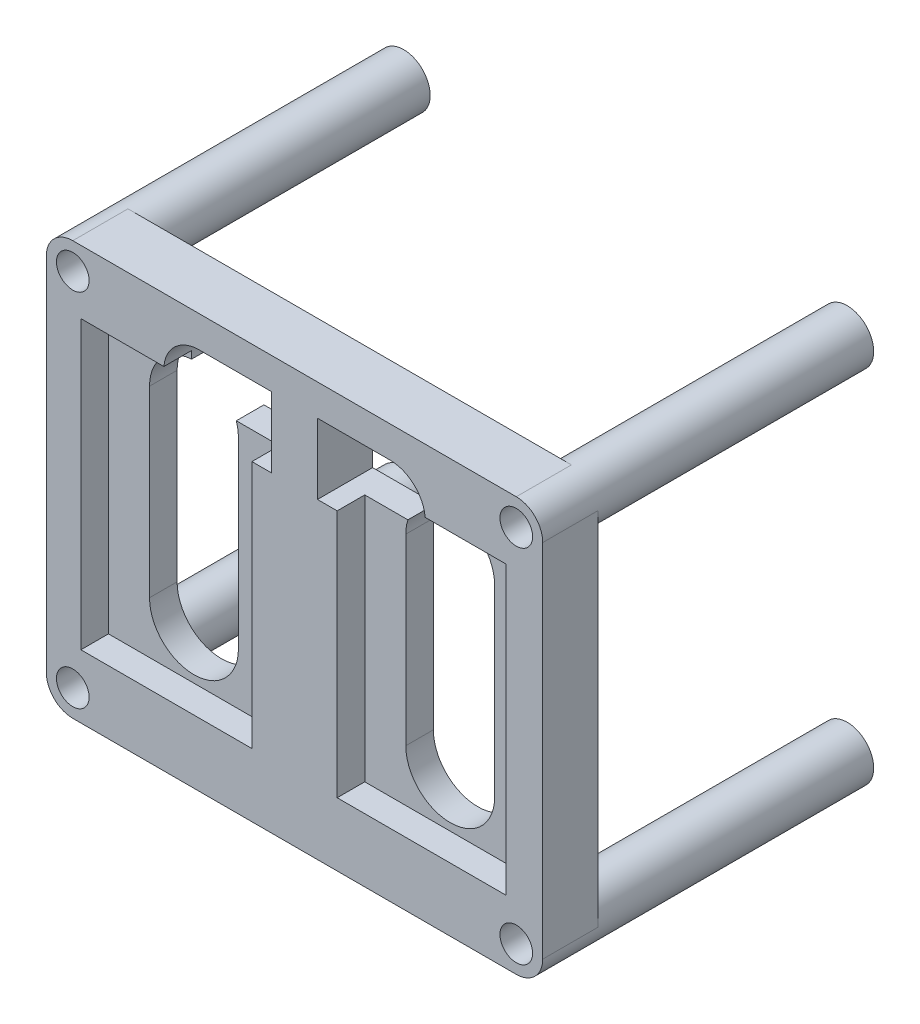
SolidWorks part; units mm, degrees
ref_plane "Front Plane" through (0, 0, 0) normal (0, 0, 1) x (1, 0, 0)
ref_plane "Top Plane" through (0, 0, 0) normal (0, 1, 0) x (1, 0, 0)
ref_plane "Right Plane" through (0, 0, 0) normal (1, 0, 0) x (0, 0, -1)
other "Configuration Table"
sketch "草图1" plane through (0, 0, 0) normal (0, 0, 1) x (1, 0, 0)
  line L0 (0, 0) -> (83.8895, 0) construction
  line L1 (-80.4073, 75) -> (80.4073, 75)
  line L2 (-90, 65.4073) -> (-90, -65.4073)
  line L3 (-80.4073, -75) -> (80.4073, -75)
  line L4 (90, 65.4073) -> (90, -65.4073)
  line L5 (-90, 75) -> (90, -75) construction
  line L6 (-90, -75) -> (90, 75) construction
  line L7 (0, 0) -> (0, -55.7173) construction
  line L8 (-77.464, 52) -> (-15.464, 52)
  line L9 (-77.464, -52) -> (-15.464, -52)
  line L10 (-77.464, 52) -> (-77.464, -52)
  line L11 (76.7565, -52) -> (76.7565, 52)
  line L12 (-15.464, 52) -> (-15.464, -52)
  line L13 (15.464, 52) -> (15.464, -52)
  line L14 (15.464, 52) -> (76.7565, 52)
  line L15 (15.464, -52) -> (76.7565, -52)
  line L16 (-46.464, 52) -> (-46.464, -52) construction
  line L17 (46.1102, -52) -> (46.1102, 52) construction
  line L18 (-46.464, 33.2159) -> (-46.464, -33.2159) construction
  line L19 (-30.3483, 33.2159) -> (-30.3483, -33.2159)
  line L20 (-62.5796, 33.2159) -> (-62.5796, -33.2159)
  line L21 (46.464, 33.2159) -> (46.464, -33.2159) construction
  line L22 (30.3483, 33.2159) -> (30.3483, -33.2159)
  line L23 (62.5796, 33.2159) -> (62.5796, -33.2159)
  line L24 (34.6697, 50.8589) -> (-34.6697, 50.8589) construction
  line L25 (34.6697, 38.0987) -> (-34.6697, 38.0987)
  line L26 (34.6697, 63.6191) -> (-34.6697, 63.6191)
  line L27 (0, 38.0987) -> (0, 63.6191) construction
  line L28 (-8.3233, 38.0987) -> (-8.3233, 63.6191)
  line L29 (8.3233, 38.0987) -> (8.3233, 63.6191)
  arc A1 (-80.4073, 75) -> (-90, 65.4073) centre (-80.4073, 65.4073) ccw
  arc A2 (80.4073, 75) -> (90, 65.4073) centre (80.4073, 65.4073) cw
  arc A3 (-80.4073, -75) -> (-90, -65.4073) centre (-80.4073, -65.4073) cw
  arc A4 (80.4073, -75) -> (90, -65.4073) centre (80.4073, -65.4073) ccw
  arc A5 (-30.3483, 33.2159) -> (-62.5796, 33.2159) centre (-46.464, 33.2159) ccw
  arc A6 (-62.5796, -33.2159) -> (-30.3483, -33.2159) centre (-46.464, -33.2159) ccw
  arc A7 (30.3483, 33.2159) -> (62.5796, 33.2159) centre (46.464, 33.2159) cw
  arc A8 (62.5796, -33.2159) -> (30.3483, -33.2159) centre (46.464, -33.2159) cw
  circle A9 centre (-80.4073, 65.4073) radius 9.5927
  circle A10 centre (80.4073, 65.4073) radius 9.5927
  circle A11 centre (-80.4073, -65.4073) radius 9.5927
  circle A12 centre (80.4073, -65.4073) radius 9.5927
  arc A13 (34.6697, 38.0987) -> (34.6697, 63.6191) centre (34.6697, 50.8589) ccw
  arc A14 (-34.6697, 63.6191) -> (-34.6697, 38.0987) centre (-34.6697, 50.8589) ccw
  arc A15 (-8.3233, 38.0987) -> (8.3233, 38.0987) centre (0, 38.0987) ccw
  arc A16 (8.3233, 63.6191) -> (-8.3233, 63.6191) centre (0, 63.6191) ccw
  circle A17 centre (-80.4073, 65.4073) radius 5.9233
  circle A18 centre (80.4073, 65.4073) radius 5.9233
  circle A19 centre (-80.4073, -65.4073) radius 5.9233
  circle A20 centre (80.4073, -65.4073) radius 5.9233
  point P0 (0, 0)
  point P36 (-46.464, 0)
  point P43 (46.464, 0)
  point P55 (0, 50.8589)
  point P61 (0, 50.8589)
  dimension "D1" = 62
  dimension "D3" = 52
extrude "凸台-拉伸1" add sketch "草图1" along normal blind 20 contours A12 L4 A10 L1 A9 L2 A11 L3 L8 L12 L9 L10 L15 L13 L14 L11 region at (0.5038, -7.9832, 0)
extrude "凸台-拉伸2" add sketch "草图1<3>" along normal blind 10 contours L13 L15 L11 L14 L23 A8 L22 A7 | L12 L8 L10 L9 A6 L20 A5 L19 region at (-62.4214, 50.7892, 0) region at (23.2849, 36.8915, 0)
sketch "草图1<3>" plane through (0, 0, 0) normal (0, 0, 1) x (1, 0, 0) same geometry as "草图1"
extrude "凸台-拉伸3" add sketch "草图1<4>" along normal blind 20 contours L25 A13 A7 | A7 A13 L14 L13 L25 | L14 A13 L26 L29 L25 L13 | L26 A14 L8 L12 L25 L28 | L8 A14 A5 L25 L12 | A5 A14 L25 region at (-23.6937, 55.1681, 0) region at (-27.2493, 46.0388, 0) region at (-39.5405, 43.4824, 0) region at (23.6937, 55.1681, 0) region at (27.2493, 46.0388, 0) region at (39.5405, 43.4824, 0)
sketch "草图1<4>" plane through (0, 0, 0) normal (0, 0, 1) x (1, 0, 0) same geometry as "草图1"
extrude "切除-拉伸4" cut sketch "草图1<8>" against normal mid plane 10 contours L14 A13 L26 L29 L25 L13 | A7 A13 L14 L13 L25 | L25 A13 A7 | A5 A14 L25 | L8 A14 A5 L25 L12 | L26 A14 L8 L12 L25 L28 region at (-23.6937, 55.1681, 0) region at (-27.2493, 46.0388, 0) region at (-39.5405, 43.4824, 0) region at (23.6937, 55.1681, 0) region at (27.2493, 46.0388, 0) region at (39.5405, 43.4824, 0)
sketch "草图1<8>" plane through (0, 0, 0) normal (0, 0, 1) x (1, 0, 0) same geometry as "草图1"
extrude "凸台-拉伸5" add sketch "草图1<11>" against normal blind 100 contours A11 A3 A19 | A1 A9 A17 | A10 A2 A18 | A4 A12 A20 region at (-73.8162, 71.9985, 0) region at (86.9985, 71.9985, 0) region at (-80.4073, -56.086, 0) region at (86.9985, -71.9985, 0)
sketch "草图1<11>" plane through (0, 0, 0) normal (0, 0, 1) x (1, 0, 0) same geometry as "草图1"
extrude "切除-拉伸5" cut sketch "草图1<14>" along normal through all and the other way blind 12 contours L25 A13 A7 | A7 A13 L14 L13 L25 | L14 A13 L26 L29 L25 L13 | L8 A14 A5 L25 L12 | L26 A14 L8 L12 L25 L28 | A5 A14 L25 region at (-23.6937, 55.1681, 0) region at (-27.2493, 46.0388, 0) region at (-39.5405, 43.4824, 0) region at (23.6937, 55.1681, 0) region at (27.2493, 46.0388, 0) region at (39.5405, 43.4824, 0)
sketch "草图1<14>" plane through (0, 0, 0) normal (0, 0, 1) x (1, 0, 0) same geometry as "草图1"
extrude "凸台-拉伸7" add sketch "草图1<15>" along normal blind 20 contours A1 A9 A17 | A11 A3 A19 | A4 A12 A20 | L26 A16 | L25 A15 | A10 A2 A18 | L25 L29 L26 L28 region at (-73.8162, 71.9985, 0) region at (86.9985, 71.9985, 0) region at (-80.4073, -56.086, 0) region at (86.9985, -71.9985, 0) region at (0, 67.1516, 0) region at (0, 50.8589, 0) region at (0, 34.5662, 0)
sketch "草图1<15>" plane through (0, 0, 0) normal (0, 0, 1) x (1, 0, 0) same geometry as "草图1"
